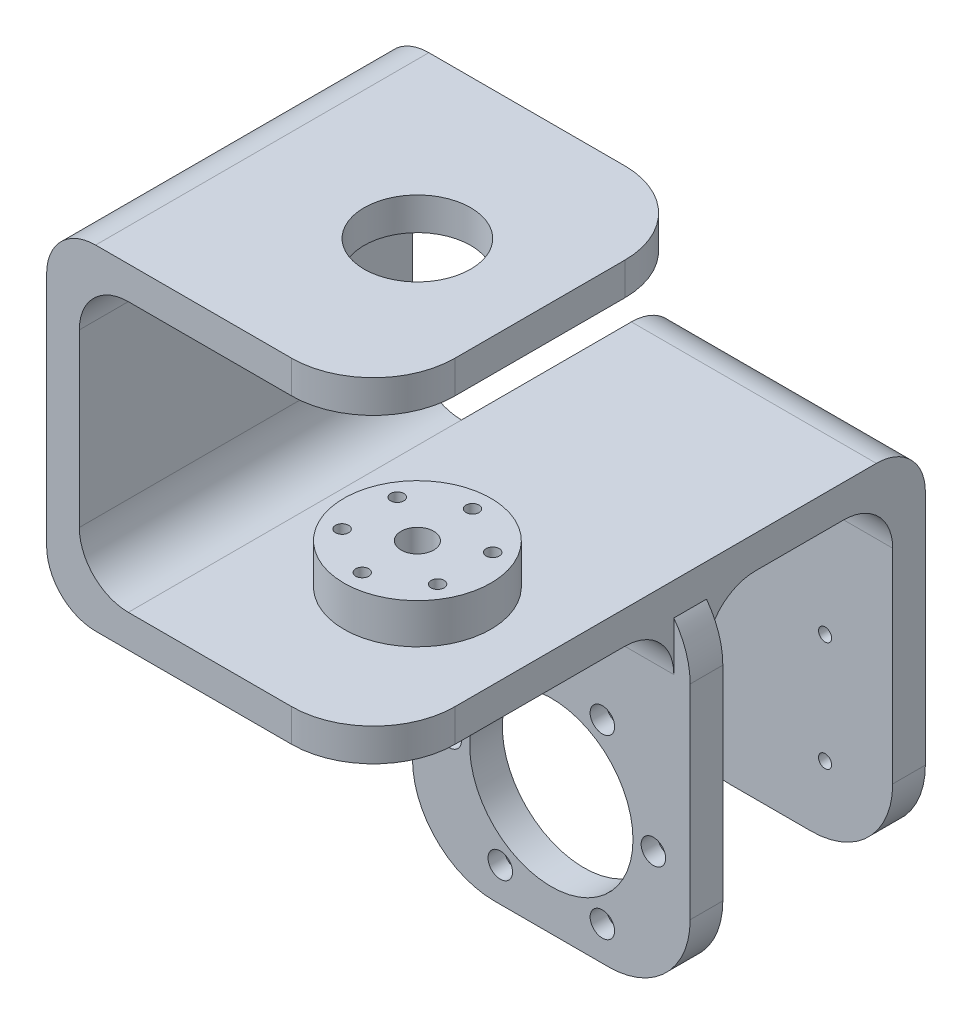
SolidWorks part; units mm, degrees
material "PETG-CF"
ref_plane "前视基准面" through (0, 0, 0) normal (0, 0, 1) x (1, 0, 0)
ref_plane "上视基准面" through (0, 0, 0) normal (0, 1, 0) x (1, 0, 0)
ref_plane "右视基准面" through (0, 0, 0) normal (1, 0, 0) x (0, 0, -1)
other "Configuration Table"
sketch "草图1" plane through (0, 0, 0) normal (0, 1, 0) x (1, 0, 0)
  line L1 (40, -40.8) -> (-40, -40.8)
  line L2 (40, -40.8) -> (40, 40.8)
  line L3 (40, 40.8) -> (-40, 40.8)
  line L4 (-40, -40.8) -> (-40, 40.8)
  line L5 (40, -40.8) -> (-40, 40.8) construction
  line L6 (40, 40.8) -> (-40, -40.8) construction
  point P0 (0, 0)
  dimension "D1" = 81.6
  dimension "D2" = 80
extrude "凸台-拉伸1" add sketch "草图1" along normal blind 8
sketch "草图2" plane through (0, 8, 0) normal (0, 1, 0) x (1, 0, 0)
  line L0 (-40, 40.8) -> (-40, -40.8) construction
  line L1 (-32, -40.8) -> (-40, -40.8)
  line L2 (-32, -40.8) -> (-32, 40.8)
  line L3 (-32, 40.8) -> (-40, 40.8)
  line L4 (-40, -40.8) -> (-40, 40.8)
  line L5 (-32, -40.8) -> (-40, 40.8) construction
  line L6 (-32, 40.8) -> (-40, -40.8) construction
  line L7 (40, 40.8) -> (-40, 40.8) construction
  line L8 (-40, -40.8) -> (40, -40.8) construction
  point P0 (-36, 0)
  dimension "D1" = 8
extrude "凸台-拉伸2" add sketch "草图2" along normal blind 52.9
sketch "草图10" plane through (0, 60.9, 0) normal (0, 1, 0) x (1, 0, 0)
  line L0 (-40, -40.8) -> (-40, 40.8) construction
  line L1 (-32, -40.8) -> (-40, -40.8)
  line L2 (-32, -40.8) -> (-32, 40.8)
  line L3 (-32, 40.8) -> (-40, 40.8)
  line L4 (-40, -40.8) -> (-40, 40.8)
  line L5 (-32, -40.8) -> (-40, 40.8) construction
  line L6 (-32, 40.8) -> (-40, -40.8) construction
  line L7 (-32, 40.8) -> (-40, 40.8) construction
  line L8 (-32, -40.8) -> (-32, 40.8) construction
  line L9 (-32, -40.8) -> (-40, -40.8) construction
  point P0 (-36, 0)
extrude "凸台-拉伸7" add sketch "草图10" along normal blind 13
sketch "草图11" plane through (0, 73.9, 0) normal (0, 1, 0) x (1, 0, 0)
  line L0 (-40, -40.8) -> (-40, 40.8) construction
  line L1 (40, -40.8) -> (-40, -40.8)
  line L2 (40, -40.8) -> (40, 40.8)
  line L3 (40, 40.8) -> (-40, 40.8)
  line L4 (-40, -40.8) -> (-40, 40.8)
  line L5 (40, -40.8) -> (-40, 40.8) construction
  line L6 (40, 40.8) -> (-40, -40.8) construction
  line L7 (40, -40.8) -> (40, 40.8) construction
  line L8 (40, 40.8) -> (-40, 40.8) construction
  line L9 (40, -40.8) -> (-40, -40.8) construction
  point P0 (0, 0)
extrude "凸台-拉伸8" add sketch "草图11" along normal blind 8
sketch "草图6" plane through (0, 8, 0) normal (0, 1, 0) x (1, 0, 0)
  line L1 (40, 40.8) -> (-40, 40.8) construction
  line L3 (40, -40.8) -> (40, 40.8) construction
  circle A0 centre (10, 0) radius 18
  point P2 (0, 40.8)
  point P3 (40, 0)
  point P6 (10, 40.8)
  dimension "D3" = 36
  dimension "D1" = 10
extrude "凸台-拉伸4" add sketch "草图6" along normal blind 9.8
sketch "草图4" plane through (0, 8, 0) normal (0, 1, 0) x (1, 0, 0)
  line L2 (40, -40.8) -> (40, 40.8) construction
  line L3 (40, 40.8) -> (-40, 40.8) construction
  circle A0 centre (10, 0) radius 13.5 construction
  circle A1 centre (10, 13.5) radius 1.6
  circle A2 centre (21.6913, 6.75) radius 1.6
  circle A3 centre (21.6913, -6.75) radius 1.6
  circle A4 centre (10, -13.5) radius 1.6
  circle A5 centre (-1.6913, -6.75) radius 1.6
  circle A6 centre (-1.6913, 6.75) radius 1.6
  circle A7 centre (10, 0) radius 4
  point P2 (40, 0)
  point P3 (10, 40.8)
  point P9 (0, 40.8)
  point P21 (10, 0)
  dimension "D1" = 27
  dimension "D4" = 3.2
  dimension "D6" = 8
  dimension "D2" = 10
  dimension "D5" = 6
extrude "切除-拉伸1" cut sketch "草图4" against normal through all and the other way up to next
sketch "草图12" plane through (0, 73.9, 0) normal (0, -1, 0) x (-1, 0, 0)
  circle A0 centre (-10, 0) radius 13.05
  dimension "D1" = 26.1
extrude "切除-拉伸3" cut sketch "草图12" against normal up to next
sketch "草图21" plane through (0, 0, 0) normal (0, -1, 0) x (-1, 0, 0)
  circle A0 centre (-10, -13.5) radius 3
  circle A1 centre (-21.6913, -6.75) radius 3
  circle A2 centre (-21.6913, 6.75) radius 3
  circle A3 centre (-10, 13.5) radius 3
  circle A4 centre (1.6913, 6.75) radius 3
  circle A5 centre (1.6913, -6.75) radius 3
  point P16 (-10, 0)
  dimension "D1" = 6
  dimension "D2" = 6
extrude "切除-拉伸10" cut sketch "草图21" against normal blind 4
sketch "Sketch1" plane through (0, 0, 0) normal (0, -1, 0) x (-1, 0, 0)
  line L1 (24, 32.8) -> (-44, 32.8)
  line L2 (24, 32.8) -> (24, 40.8)
  line L3 (24, 40.8) -> (-44, 40.8)
  line L4 (-44, 32.8) -> (-44, 40.8)
  line L9 (-40, -40.8) -> (-40, 40.8) construction
  point P5 (0, 0)
  point P6 (0, 0)
  point P8 (-10, 32.8)
  point P9 (0, 0)
  point P10 (0, 0)
  point P11 (0, 0)
  point P12 (0, 0)
  point P18 (0, 0)
  point P19 (30.4547, 32.8)
  dimension "D1" = 8
  dimension "D2" = 4
extrude "Boss-Extrude1" add sketch "Sketch1" along normal blind 82
sketch "Sketch2" plane through (0.8, 0, -40.8) normal (0, 0, 1) x (1, 0, 0)
  line L1 (-20.8, 0) -> (39.2, 0)
  line L2 (-20.8, 0) -> (-20.8, 8)
  line L3 (-20.8, 8) -> (39.2, 8)
  line L4 (39.2, 0) -> (39.2, 8)
  point P4 (-20.8, 0)
  point P5 (9.2, 0)
  point P6 (0, 0)
  dimension "D1" = 8
extrude "Boss-Extrude2" add sketch "Sketch2" against normal blind 53.6
sketch "Sketch3" plane through (0, 94.4, -94.4) normal (0, 0, 1) x (-1, 0, 0)
  line L0 (20, 94.4) -> (20, 86.4) construction
  line L5 (-44, 176.4) -> (24, 176.4) construction
  line L6 (-40, 86.4) -> (20, 86.4)
  line L7 (-40, 86.4) -> (-40, 176.4)
  line L8 (-40, 176.4) -> (20, 176.4)
  line L9 (20, 86.4) -> (20, 176.4)
  point P4 (0, 0)
  point P5 (40, 166.4)
  point P6 (0, 0)
extrude "Boss-Extrude3" add sketch "Sketch3" along normal blind 8
sketch "Sketch4" plane through (7.2, 0, -32.8) normal (0, 0, 1) x (1, 0, 0)
  line L1 (36.8, -82) -> (-31.2, -82) construction
  circle A0 centre (2.8, -52) radius 20
  circle A2 centre (27.8, -52) radius 1.6
  circle A3 centre (2.8, -52) radius 25 construction
  circle A4 centre (15.3, -73.6506) radius 1.6
  circle A5 centre (-9.7, -73.6506) radius 1.6
  circle A6 centre (-22.2, -52) radius 1.6
  circle A7 centre (-9.7, -30.3494) radius 1.6
  circle A8 centre (15.3, -30.3494) radius 1.6
  point P20 (2.8, -52)
  dimension "D2" = 40
  dimension "D3" = 3.2
  dimension "D4" = 50
  dimension "D1" = 30
  dimension "D5" = 6
extrude "Cut-Extrude1" cut sketch "Sketch4" against normal up to next
sketch "Sketch5" plane through (46.4, 0, -86.4) normal (0, 0, 1) x (1, 0, 0)
  line L1 (-36.4, 0) -> (-36.4, -52) construction
  line L2 (-49.835, -38.565) -> (-36.4, -52) construction
  circle A0 centre (-36.4, -52) radius 19 construction
  circle A1 centre (-49.835, -38.565) radius 1.6
  circle A2 centre (-22.965, -38.565) radius 1.6
  circle A3 centre (-22.965, -65.435) radius 1.6
  circle A4 centre (-49.835, -65.435) radius 1.6
  point P4 (-46.4, -42)
  point P5 (0, 0)
  point P17 (-36.4, -52)
  dimension "D1" = 38
  dimension "D3" = 3.2
  dimension "D4" = 45
  dimension "D5" = 4
extrude "Cut-Extrude2" cut sketch "Sketch5" against normal up to next
sketch "Sketch6" plane through (0, 0, -94.4) normal (0, 0, -1) x (-1, 0, 0)
  circle A0 centre (-23.435, -38.565) radius 3
  circle A1 centre (3.435, -38.565) radius 3
  circle A2 centre (3.435, -65.435) radius 3
  circle A3 centre (-23.435, -65.435) radius 3
  point P12 (-10, -52)
  dimension "D1" = 6
  dimension "D2" = 4
extrude "Cut-Extrude3" cut sketch "Sketch6" against normal blind 4
sketch "Sketch7" plane through (72.8, 0, -32.8) normal (0, 0, -1) x (-1, 0, 0)
  circle A0 centre (75.3, -30.3494) radius 3
  circle A1 centre (87.8, -52) radius 3
  circle A2 centre (75.3, -73.6506) radius 3
  circle A3 centre (50.3, -73.6506) radius 3
  circle A4 centre (37.8, -52) radius 3
  circle A5 centre (50.3, -30.3494) radius 3
  point P15 (62.8, -52)
  dimension "D1" = 6
  dimension "D2" = 6
extrude "Cut-Extrude4" cut sketch "Sketch7" along normal blind 4
fillet "Fillet1" radius 12 8 edges at (-32, 73.9, 0) (-32, 8, 0) (-40, 81.9, 0) (10, 8, -94.4) (-40, 0, 0) (10, 0, -40.8) (10, 0, -86.4) (8, 0, -32.8)
fillet "Fillet2" radius 20 8 edges at (40, 4, 40.8) (40, 77.9, 40.8) (40, 77.9, -40.8) (-20, -82, -90.4) (-24, -82, -36.8) (40, -82, -90.4) (44, -82, -36.8) (44, 0, -36.8)
